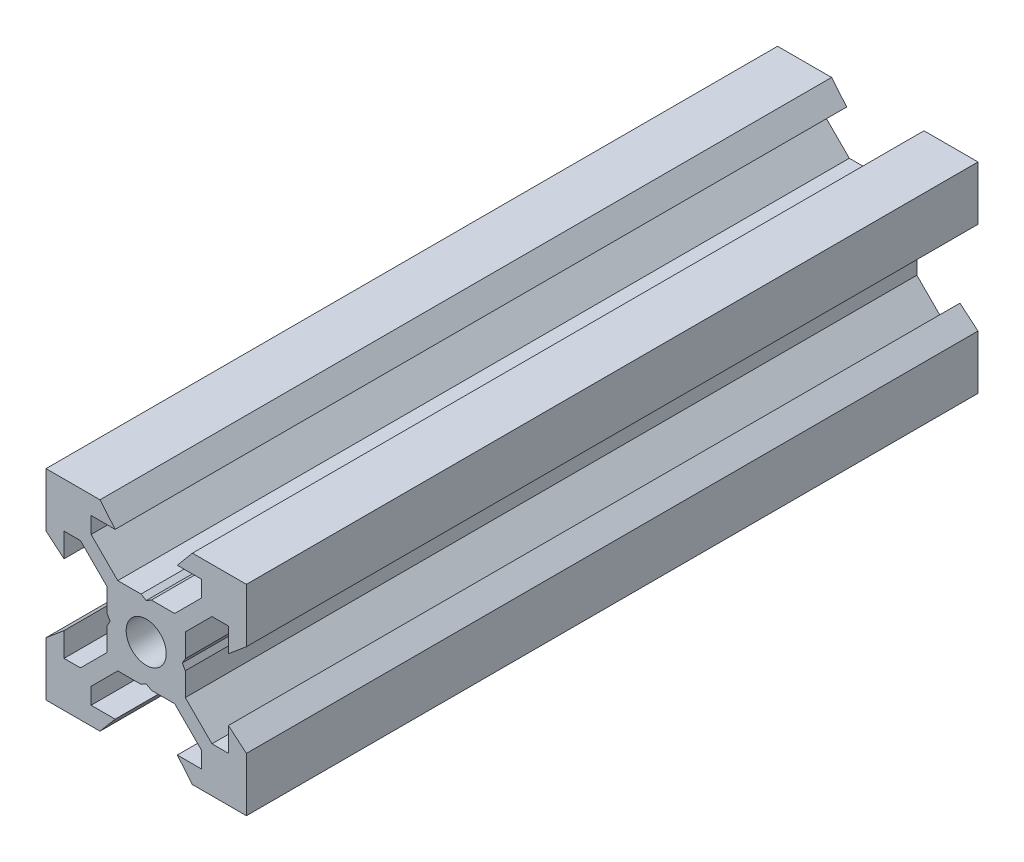
SolidWorks part; units mm, degrees
ref_plane "Front Plane" through (0, 0, 0) normal (0, 0, 1) x (1, 0, 0)
ref_plane "Top Plane" through (0, 0, 0) normal (0, 1, 0) x (1, 0, 0)
ref_plane "Right Plane" through (0, 0, 0) normal (1, 0, 0) x (0, 0, -1)
sketch "Sketch1" plane through (0, 0, 0) normal (0, 0, 1) x (1, 0, 0)
  line L0 (10, 10) -> (4.6104, 10) construction
  line L1 (10, 10) -> (10, 4.6104) construction
  line L2 (10, -10) -> (10, -4.6104) construction
  line L3 (10, -10) -> (4.6104, -10) construction
  line L4 (10, 10) -> (10, 4.6104)
  line L5 (6.5607, 5.5) -> (8.2, 5.5)
  line L6 (5.5, 8.2) -> (5.5, 6.5607)
  line L7 (10, 10) -> (4.6104, 10)
  line L8 (10, 10) -> (10, 4.6104)
  line L9 (6.5607, 5.5) -> (3.9, 2.8393)
  line L10 (5.5, 6.5607) -> (2.8393, 3.9)
  line L11 (10, 4.6104) -> (8.2, 3.1)
  line L12 (4.6104, 10) -> (3.1, 8.2)
  line L13 (8.2, 3.1) -> (8.2, 5.5)
  line L14 (3.1, 8.2) -> (5.5, 8.2)
  line L15 (-6.5607, 5.5) -> (-8.2, 5.5)
  line L16 (6.5607, -5.5) -> (8.2, -5.5)
  line L17 (3.1, -8.2) -> (5.5, -8.2)
  line L18 (8.2, -3.1) -> (8.2, -5.5)
  line L19 (4.6104, -10) -> (3.1, -8.2)
  line L20 (10, -4.6104) -> (8.2, -3.1)
  line L21 (0.5196, -3.9) -> (0, -3.6)
  line L22 (0.5196, 3.9) -> (0, 3.6)
  line L23 (3.6, 0) -> (3.9, -0.5196)
  line L24 (3.9, 0.5196) -> (3.6, 0)
  line L25 (3.9, 0.5196) -> (3.9, 2.8393)
  line L26 (2.8393, 3.9) -> (0.5196, 3.9)
  line L27 (3.9, -2.8393) -> (3.9, -0.5196)
  line L28 (2.8393, -3.9) -> (0.5196, -3.9)
  line L29 (5.5, -6.5607) -> (2.8393, -3.9)
  line L30 (6.5607, -5.5) -> (3.9, -2.8393)
  line L31 (10, -10) -> (10, -4.6104)
  line L32 (10, -10) -> (4.6104, -10)
  line L33 (5.5, -8.2) -> (5.5, -6.5607)
  line L34 (-6.5607, -5.5) -> (-8.2, -5.5)
  line L35 (10, -10) -> (10, -4.6104)
  line L36 (0, 0) -> (0, 8.2) construction
  line L37 (-10, -10) -> (-4.6104, -10) construction
  line L38 (-10, -10) -> (-10, -4.6104) construction
  line L39 (-10, 10) -> (-10, 4.6104) construction
  line L40 (-10, 10) -> (-4.6104, 10) construction
  line L41 (-10, -10) -> (-10, -4.6104)
  line L43 (-5.5, -8.2) -> (-5.5, -6.5607)
  line L44 (-10, -10) -> (-4.6104, -10)
  line L45 (-10, -10) -> (-10, -4.6104)
  line L46 (-6.5607, -5.5) -> (-3.9, -2.8393)
  line L47 (-5.5, -6.5607) -> (-2.8393, -3.9)
  line L48 (-2.8393, -3.9) -> (-0.5196, -3.9)
  line L49 (-3.9, -2.8393) -> (-3.9, -0.5196)
  line L50 (-2.8393, 3.9) -> (-0.5196, 3.9)
  line L51 (-3.9, 0.5196) -> (-3.9, 2.8393)
  line L52 (-3.9, 0.5196) -> (-3.6, 0)
  line L53 (-3.6, 0) -> (-3.9, -0.5196)
  line L54 (-0.5196, 3.9) -> (0, 3.6)
  line L55 (-0.5196, -3.9) -> (0, -3.6)
  line L56 (-10, -4.6104) -> (-8.2, -3.1)
  line L57 (-4.6104, -10) -> (-3.1, -8.2)
  line L58 (-8.2, -3.1) -> (-8.2, -5.5)
  line L59 (-3.1, -8.2) -> (-5.5, -8.2)
  line L60 (-10, -10) -> (10, -10) construction
  line L61 (-10, -10) -> (-10, 10) construction
  line L62 (-3.1, 8.2) -> (-5.5, 8.2)
  line L63 (-8.2, 3.1) -> (-8.2, 5.5)
  line L64 (-4.6104, 10) -> (-3.1, 8.2)
  line L65 (-10, 4.6104) -> (-8.2, 3.1)
  line L66 (-5.5, 6.5607) -> (-2.8393, 3.9)
  line L67 (-6.5607, 5.5) -> (-3.9, 2.8393)
  line L68 (-10, 10) -> (-10, 4.6104)
  line L69 (-10, 10) -> (-4.6104, 10)
  line L70 (-5.5, 8.2) -> (-5.5, 6.5607)
  line L71 (-10, 10) -> (10, 10) construction
  line L72 (-10, 10) -> (-10, 4.6104)
  line L73 (10, -10) -> (10, 10) construction
  line L74 (-10, -10) -> (10, 10) construction
  line L75 (-10, 10) -> (10, -10) construction
  circle A0 centre (0, 0) radius 2
  dimension "D7" = 4
  dimension "D1" = 20
  dimension "D2" = 5.3896
  dimension "D3" = 4.5
  dimension "D4" = 50
  dimension "D5" = 1.8
  dimension "D6" = 1.5104
  dimension "D8" = 5.5
  dimension "D9" = 120
  dimension "D10" = 0.3
  dimension "D11" = 2.3197
  dimension "D12" = 7.8
  dimension "D13" = 7.8
  dimension "D14" = 1.5
  dimension "D15" = 2.6607
extrude "Boss-Extrude1" add sketch "Sketch1" along normal mid plane 73 contours L70 L62 L64 L69 L68 L65 L63 L15 L67 L51 L52 L53 L49 L46 L34 L58 L56 L41 L44 L57 L59 L43 L47 L48 L55 L21 L28 L29 L33 L17 L19 L32 L31 L20 L18 L16 L30 L27 L23 L24 L25 L9 L5 L13 L11 L4 L7 L12 L14 L6 L10 region at (9.7172, 7.3052, 0)
